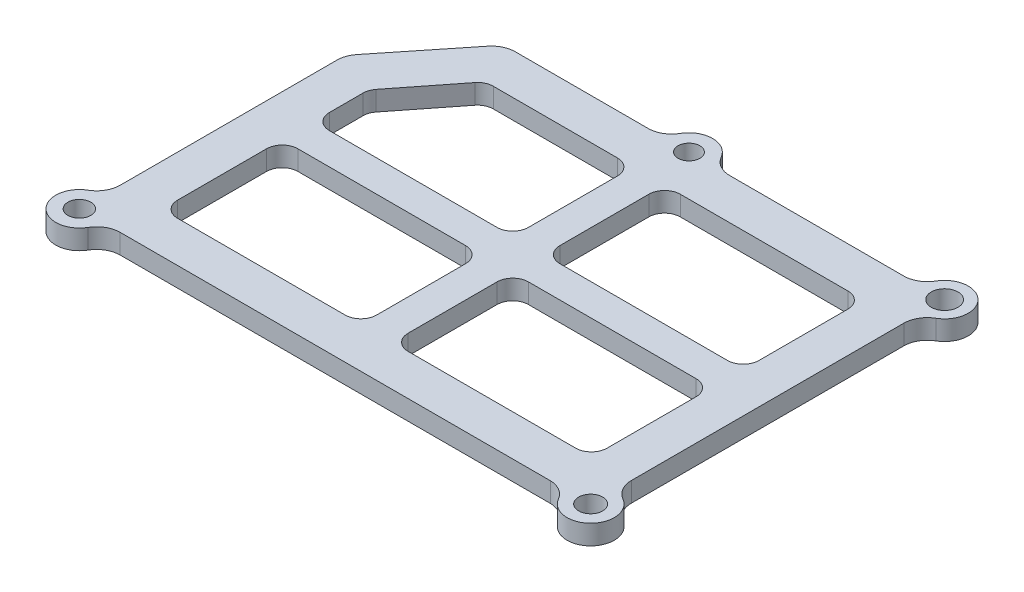
SolidWorks part; units mm, degrees
material "ABS"
ref_plane "Front Plane" through (0, 0, 0) normal (0, 0, 1) x (1, 0, 0)
ref_plane "Top Plane" through (0, 0, 0) normal (0, 1, 0) x (1, 0, 0)
ref_plane "Right Plane" through (0, 0, 0) normal (1, 0, 0) x (0, 0, -1)
sketch "Sketch1" plane through (0, 0, 0) normal (0, 1, 0) x (1, 0, 0)
  line L0 (-59.8038, -22.5) -> (-5.1032, -22.5)
  line L1 (0, -17.3038) -> (0, 17.3038)
  line L2 (-5.1962, 22.5) -> (-27.3038, 22.5)
  line L3 (-37.6962, 22.5) -> (-54.5941, 22.5)
  line L10 (-65, 10.247) -> (-65, -17.3038)
  line L11 (-32.5, 22.5) -> (0, 22.5) construction
  line L12 (0, 22.5) -> (0, -22.5) construction
  line L13 (0, -22.5) -> (-65, -22.5) construction
  line L14 (-64.3422, 12.1216) -> (-56.9363, 21.3746)
  line L22 (-59.2828, 9.519) -> (-53.7592, 16.5404)
  line L23 (-57.7108, -17.3038) -> (-36.407, -17.3038)
  line L24 (-59.7108, -15.3038) -> (-59.7108, -4)
  line L25 (-52.1873, 17.3038) -> (-36.407, 17.3038)
  line L26 (-5.1032, -15.3038) -> (-5.1032, -4)
  line L27 (-28.407, -17.3038) -> (-7.1032, -17.3038)
  line L28 (-30.407, -15.3038) -> (-30.407, -4)
  line L29 (-34.407, -15.3038) -> (-34.407, -4)
  line L30 (-28.407, 17.3038) -> (-7.1032, 17.3038)
  line L31 (-36.407, -2) -> (-57.7108, -2)
  line L32 (-7.1032, 2) -> (-28.407, 2)
  line L33 (-7.1032, -2) -> (-28.407, -2)
  line L34 (-59.7108, 4) -> (-59.7108, 8.2824)
  line L35 (-36.407, 2) -> (-57.7108, 2)
  line L36 (-34.407, 4) -> (-34.407, 15.3038)
  line L37 (-30.407, 4) -> (-30.407, 15.3038)
  line L38 (-5.1032, 4) -> (-5.1032, 15.3038)
  arc A0 (-59.8038, -22.5) -> (-62.4019, -24) centre (-59.8038, -25.5) ccw
  arc A1 (-2.5981, -24) -> (-5.1032, -22.5) centre (-5.197, -25.4985) ccw
  arc A2 (-2.5981, -24) -> (1.5, -19.9019) centre (0, -22.5) ccw
  arc A3 (0, -17.3038) -> (1.5, -19.9019) centre (3, -17.3038) ccw
  arc A4 (1.5, 19.9019) -> (0, 17.3038) centre (3, 17.3038) ccw
  arc A5 (1.5, 19.9019) -> (-2.5981, 24) centre (0, 22.5) ccw
  arc A6 (-5.1962, 22.5) -> (-2.5981, 24) centre (-5.1962, 25.5) ccw
  arc A7 (-29.9019, 24) -> (-27.3038, 22.5) centre (-27.3038, 25.5) ccw
  arc A8 (-29.9019, 24) -> (-35.0981, 24) centre (-32.5, 22.5) ccw
  arc A9 (-37.6962, 22.5) -> (-35.0981, 24) centre (-37.6962, 25.5) ccw
  arc A17 (-66.5, -19.9019) -> (-65, -17.3038) centre (-68, -17.3038) ccw
  arc A18 (-66.5, -19.9019) -> (-62.4019, -24) centre (-65, -22.5) ccw
  circle A19 centre (-65, -22.5) radius 1.4605
  circle A20 centre (0, -22.5) radius 1.5295
  circle A21 centre (0, 22.5) radius 1.6976
  circle A22 centre (-32.5, 22.5) radius 1.3878
  arc A23 (-56.9363, 21.3746) -> (-54.5941, 22.5) centre (-54.5941, 19.5) cw
  arc A24 (-64.3422, 12.1216) -> (-65, 10.247) centre (-62, 10.247) ccw
  arc A25 (-7.1032, 17.3038) -> (-5.1032, 15.3038) centre (-7.1032, 15.3038) cw
  arc A26 (-5.1032, -15.3038) -> (-7.1032, -17.3038) centre (-7.1032, -15.3038) cw
  arc A27 (-30.407, -15.3038) -> (-28.407, -17.3038) centre (-28.407, -15.3038) ccw
  arc A28 (-30.407, 15.3038) -> (-28.407, 17.3038) centre (-28.407, 15.3038) cw
  arc A29 (-59.2828, 9.519) -> (-59.7108, 8.2824) centre (-57.7108, 8.2824) ccw
  arc A30 (-52.1873, 17.3038) -> (-53.7592, 16.5404) centre (-52.1873, 15.3038) ccw
  arc A31 (-34.407, 15.3038) -> (-36.407, 17.3038) centre (-36.407, 15.3038) ccw
  arc A32 (-34.407, -15.3038) -> (-36.407, -17.3038) centre (-36.407, -15.3038) cw
  arc A33 (-59.7108, -15.3038) -> (-57.7108, -17.3038) centre (-57.7108, -15.3038) ccw
  arc A34 (-30.407, 4) -> (-28.407, 2) centre (-28.407, 4) ccw
  arc A35 (-34.407, 4) -> (-36.407, 2) centre (-36.407, 4) cw
  arc A36 (-34.407, -4) -> (-36.407, -2) centre (-36.407, -4) ccw
  arc A37 (-57.7108, -2) -> (-59.7108, -4) centre (-57.7108, -4) ccw
  arc A38 (-57.7108, 2) -> (-59.7108, 4) centre (-57.7108, 4) cw
  arc A39 (-30.407, -4) -> (-28.407, -2) centre (-28.407, -4) cw
  arc A40 (-7.1032, -2) -> (-5.1032, -4) centre (-7.1032, -4) cw
  arc A41 (-7.1032, 2) -> (-5.1032, 4) centre (-7.1032, 4) ccw
  point P75 (-34.407, 2)
  point P80 (-34.407, -2)
  dimension "D1" = 2.7757
  dimension "D7" = 3
  dimension "D8" = 3
  dimension "D9" = 3
  dimension "D10" = 3
  dimension "D11" = 3
  dimension "D12" = 3
  dimension "D13" = 3
  dimension "D14" = 3
  dimension "D15" = 3
  dimension "D16" = 3
  dimension "D17" = 3
  dimension "D18" = 3
  dimension "D2" = 3
  dimension "D3" = 2
  dimension "D19" = 2
  dimension "D20" = 2
  dimension "D4" = 65
  dimension "D5" = 45
  dimension "D6" = 32.5
extrude "Boss-Extrude1" add sketch "Sketch1" along normal blind 2.5
